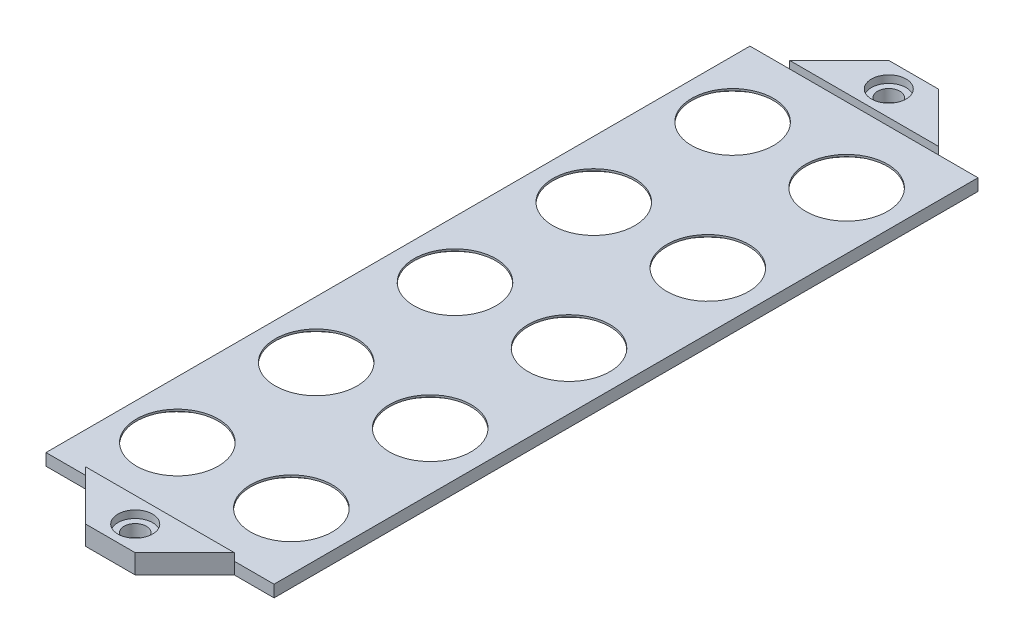
SolidWorks part; units mm, degrees
ref_plane "Front Plane" through (0, 0, 0) normal (0, 0, 1) x (1, 0, 0)
ref_plane "Top Plane" through (0, 0, 0) normal (0, 1, 0) x (1, 0, 0)
ref_plane "Right Plane" through (0, 0, 0) normal (1, 0, 0) x (0, 0, -1)
sketch "Szkic1" plane through (0, 0, 0) normal (0, 1, 0) x (1, 0, 0)
  line L0 (6.5, 25) -> (-3.5, 15)
  line L1 (-11.5, 15) -> (34.5, 15)
  line L2 (-11.5, 15) -> (-11.5, -127)
  line L3 (-11.5, -127) -> (34.5, -127)
  line L4 (34.5, 15) -> (34.5, -127)
  line L5 (6.5, 15) -> (16.5, 15)
  line L6 (6.5, 15) -> (6.5, 25)
  line L7 (6.5, 25) -> (16.5, 25)
  line L8 (16.5, 15) -> (16.5, 25)
  line L9 (16.5, 25) -> (26.5, 15)
  line L12 (-11.5, -56) -> (-33.554, -56) construction
  line L13 (16.5, -137) -> (26.5, -127)
  line L14 (16.5, -127) -> (16.5, -137)
  line L15 (6.5, -127) -> (6.5, -137)
  line L16 (6.5, -137) -> (16.5, -137)
  line L17 (6.5, -137) -> (-3.5, -127)
  line L18 (-11.5, -155) -> (34.5, -155) [skipped]
  line L19 (-11.5, -183) -> (34.5, -183) [skipped]
  circle A0 centre (0, 0) radius 8.25
  circle A1 centre (0, 0) radius 10.6
  circle A2 centre (0, 0) radius 10.1
  circle A3 centre (0, 0) radius 11
  circle A5 centre (23, 0) radius 8.25
  circle A6 centre (23, 0) radius 10.6
  circle A7 centre (23, 0) radius 10.1
  circle A8 centre (23, 0) radius 11
  circle A10 centre (23, -28) radius 8.25
  circle A11 centre (23, -28) radius 10.6
  circle A12 centre (23, -28) radius 10.1
  circle A13 centre (23, -28) radius 11
  circle A15 centre (0, -28) radius 8.25
  circle A16 centre (0, -28) radius 10.6
  circle A17 centre (0, -28) radius 10.1
  circle A18 centre (0, -28) radius 11
  circle A20 centre (0, -56) radius 11
  circle A21 centre (0, -56) radius 10.6
  circle A22 centre (0, -56) radius 10.1
  circle A23 centre (0, -56) radius 8.25
  circle A24 centre (23, -56) radius 8.25
  circle A25 centre (23, -56) radius 10.1
  circle A26 centre (23, -56) radius 10.6
  circle A27 centre (23, -56) radius 11
  circle A28 centre (0, -84) radius 11
  circle A29 centre (0, -84) radius 10.6
  circle A30 centre (0, -84) radius 10.1
  circle A31 centre (0, -84) radius 8.25
  circle A32 centre (23, -84) radius 8.25
  circle A33 centre (23, -84) radius 10.1
  circle A34 centre (23, -84) radius 10.6
  circle A35 centre (23, -84) radius 11
  circle A36 centre (0, -112) radius 11
  circle A37 centre (0, -112) radius 10.6
  circle A38 centre (0, -112) radius 10.1
  circle A39 centre (0, -112) radius 8.25
  circle A40 centre (23, -112) radius 8.25
  circle A41 centre (23, -112) radius 10.1
  circle A42 centre (23, -112) radius 10.6
  circle A43 centre (23, -112) radius 11
  dimension "D1" = 16.5
  dimension "D2" = 20.2
  dimension "D3" = 21.2
  dimension "D4" = 0.4
  dimension "D5" = 23
  dimension "D8" = 11.5
  dimension "D10" = 2
  dimension "D9" = 11.5
  dimension "D11" = 15
  dimension "D12" = 10
  dimension "D13" = 18
  dimension "D14" = 10
  dimension "D15" = 3
  dimension "D16" = 15
  dimension "D17" = 45
  dimension "D18" = 45
  dimension "D6" = 2
  dimension "D7" = 2
extrude "Dodanie-wyciągnięcie1" add sketch "Szkic1" along normal blind 0.4 contours L4 L1 L2 | L4 L2 | L2 L3 L4 | A18 | A18 A16 | A16 A17 | A17 A15 | A12 A10 | A11 A12 | A13 A11 | A13 | A7 A5 | A6 A7 | A8 A6 | A8 | A3 | A3 A1 | A1 A2 | A2 A0 | L1 L6 L0 | L1 L8 L7 L6 | L9 L8 L1 | A22 A23 | A21 A22 | A20 A21 | A25 A24 | A26 A25 | A27 A26 | A33 A32 | A34 A33 | A35 A34 | A28 A29 | A29 A30 | A30 A31 | A41 A40 | A42 A41 | A43 A42 | A38 A39 | A37 A38 | A36 A37 | L15 L16 L14 L3 | L17 L15 L3 | L3 L14 L13 region at (3.1667, 0, -18.3333) region at (11.5, 0, -20) region at (11.5, 0, 56) region at (19.8333, 0, -18.3333) region at (3.1667, 0, 130.3333) region at (11.5, 0, 132) region at (19.8333, 0, 130.3333) region at (-10.3002, 0, 0) region at (-9.8143, 0, 0) region at (-10.6889, 0, 0) region at (12.6998, 0, 0) region at (13.1857, 0, 0) region at (12.3111, 0, 0) region at (12.6998, 0, 28) region at (13.1857, 0, 28) region at (12.3111, 0, 28) region at (-10.3002, 0, 28) region at (-9.8143, 0, 28) region at (-10.6889, 0, 28) region at (-10.6889, 0, 56) region at (-10.3002, 0, 56) region at (-9.8143, 0, 56) region at (13.1857, 0, 56) region at (12.6998, 0, 56) region at (12.3111, 0, 56) region at (-10.6889, 0, 84) region at (-10.3002, 0, 84) region at (-9.8143, 0, 84) region at (13.1857, 0, 84) region at (12.6998, 0, 84) region at (12.3111, 0, 84) region at (-10.6889, 0, 112) region at (-10.3002, 0, 112) region at (-9.8143, 0, 112) region at (13.1857, 0, 112) region at (12.6998, 0, 112) region at (12.3111, 0, 112)
extrude "Dodanie-wyciągnięcie2" add sketch "Szkic1<3>" against normal blind 2 from surface contours A3 | A8 | L4 L1 L2 | L4 L2 | A18 | A13 | L2 L3 L4 | L1 L6 L0 | L1 L8 L7 L6 | L9 L8 L1 | L17 L15 L3 | L15 L16 L14 L3 | L3 L14 L13 region at (3.1667, 0, -18.3333) region at (11.5, 0, -20) region at (11.5, 0, 56) region at (19.8333, 0, -18.3333) region at (3.1667, 0, 130.3333) region at (11.5, 0, 132) region at (19.8333, 0, 130.3333) starting at face at (11.5, 0, 56)
sketch "Szkic1<3>" plane through (0, 0, 0) normal (0, 1, 0) x (1, 0, 0) same geometry as "Szkic1"
sketch "Szkic2" plane through (0, 0.4, 0) normal (0, 1, 0) x (1, 0, 0)
  line L0 (-11.5, 15) -> (34.5, 15)
  line L1 (11.5, 15) -> (11.5, 25)
  line L2 (6.5, 25) -> (16.5, 25) construction
  line L3 (-11.5, -56) -> (34.5, -56) construction
  line L4 (-11.5, 15) -> (-11.5, -127) construction
  line L5 (34.5, 15) -> (34.5, -127) construction
  circle A0 centre (11.5, 20) radius 2.25
  circle A1 centre (11.5, -132) radius 2.25
  dimension "D1" = 4.5
extrude "Wytnij-wyciągnięcie1" cut sketch "Szkic2" against normal blind 20 contours L1 A0 | L1 A0 | A1 region at (10.5451, 0.4, -20) region at (12.4549, 0.4, -20) region at (11.5, 0.4, 132)
sketch "Szkic5" plane through (0, 0.4, 0) normal (0, 1, 0) x (1, 0, 0)
  line L0 (-3.5, 15) -> (6.5, 25)
  line L1 (6.5, 25) -> (16.5, 25)
  line L2 (16.5, 25) -> (26.5, 15)
  line L3 (26.5, 15) -> (-3.5, 15)
  line L4 (-11.5, -56) -> (-35.7115, -56) construction
  line L5 (-11.5, 15) -> (-11.5, -127) construction
  line L6 (26.5, -127) -> (-3.5, -127)
  line L7 (16.5, -137) -> (26.5, -127)
  line L8 (6.5, -137) -> (16.5, -137)
  line L9 (-3.5, -127) -> (6.5, -137)
  circle A0 centre (11.5, 20) radius 2
  circle A1 centre (11.5, -132) radius 2
  circle A2 centre (11.5, -132) radius 3.5
  circle A3 centre (11.5, 20) radius 3.5
  line M3 (26.5, 15) -> (16.5, 25)
  line M4 (16.5, 25) -> (6.5, 25)
  line M5 (6.5, 25) -> (-3.5, 15)
  line M9 (-3.5, -127) -> (6.5, -137)
  line M10 (6.5, -137) -> (16.5, -137)
  line M11 (16.5, -137) -> (26.5, -127)
  dimension "D1" = 7
  dimension "D2" = 7
extrude "Dodanie-wyciągnięcie3" add sketch "Szkic5" along normal blind 1.5 contours L3 A3 M3 M4 M5 | L6 A2 M11 M9 M10 region at (1.7236, 0.4, -19.7764) region at (21.2764, 0.4, 131.7764)
